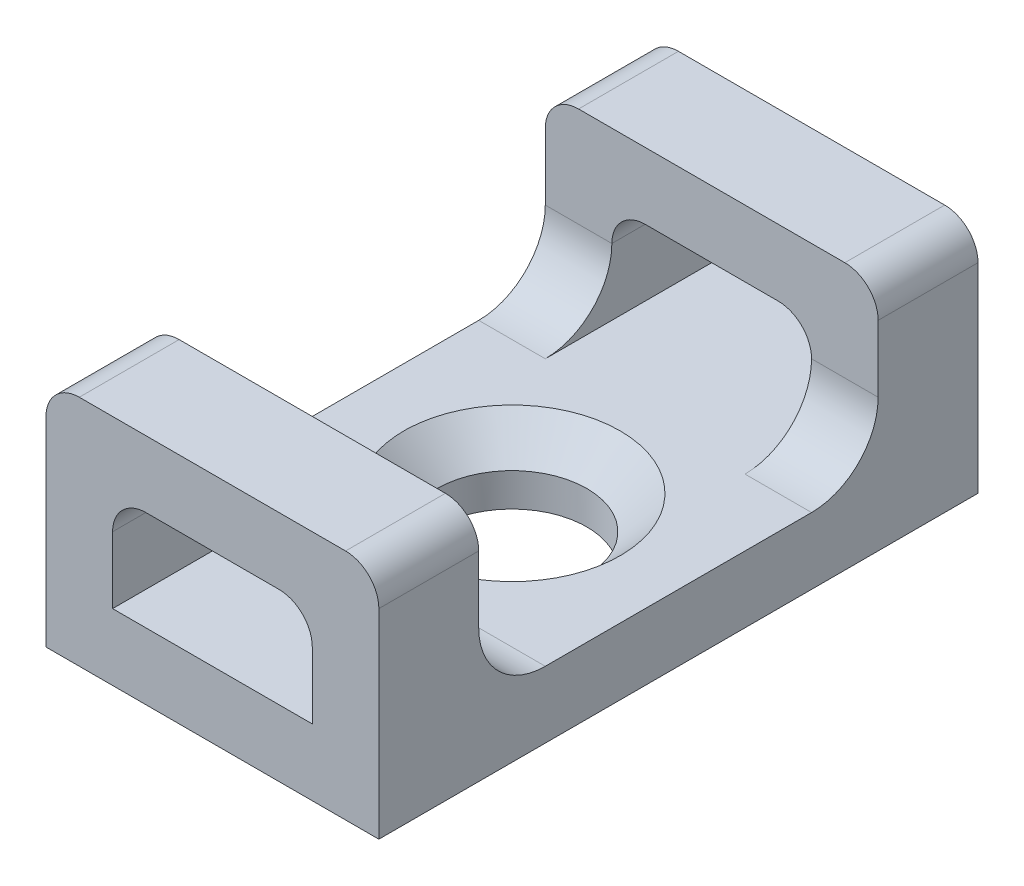
SolidWorks part; units mm, degrees
note: The reader was unsure of these and kept them because the rebuilt part matched: shared geometry of "Эскиз4<3>".
ref_plane "Спереди" through (0, 0, 0) normal (0, 0, 1) x (1, 0, 0)
ref_plane "Сверху" through (0, 0, 0) normal (0, 1, 0) x (1, 0, 0)
ref_plane "Справа" through (0, 0, 0) normal (1, 0, 0) x (0, 0, -1)
sketch "Эскиз1" plane through (0, 0, 0) normal (0, 1, 0) x (1, 0, 0)
  line L1 (0, 0) -> (10, 0)
  line L2 (0, 0) -> (0, 18)
  line L3 (0, 18) -> (10, 18)
  line L4 (10, 0) -> (10, 18)
  dimension "D1" = 18
  dimension "D2" = 10
extrude "Бобышка-Вытянуть1" add sketch "Эскиз1" along normal blind 2
sketch "Эскиз2" plane through (0, 2, 0) normal (0, 1, 0) x (1, 0, 0)
  line L0 (0, 0) -> (10, 0) construction
  line L1 (0, 18) -> (0, 0) construction
  circle A0 centre (5, 9) radius 2.25
  point P5 (5, 0)
  point P9 (0, 9)
  dimension "D1" = 4.5
extrude "Вырез-Вытянуть1" cut sketch "Эскиз2" against normal blind 2
sketch "Эскиз4" plane through (0, 0, 0) normal (0, 0, 1) x (1, 0, 0)
  line L0 (0, 2) -> (10, 2) construction
  line L1 (0, 2) -> (2, 2)
  line L2 (0, 2) -> (0, 6)
  line L3 (1, 7) -> (2, 7)
  line L4 (2, 2) -> (2, 4)
  line L5 (10, 2) -> (8, 2)
  line L6 (10, 2) -> (10, 6)
  line L7 (9, 7) -> (8, 7)
  line L8 (8, 2) -> (8, 4)
  line L9 (2, 7) -> (8, 7)
  line L10 (2, 7) -> (2, 5)
  line L11 (3, 5) -> (7, 5)
  line L12 (8, 7) -> (8, 5)
  arc A0 (10, 6) -> (9, 7) centre (9, 6) ccw
  arc A1 (1, 7) -> (0, 6) centre (1, 6) ccw
  arc A2 (8, 4) -> (7, 5) centre (7, 4) ccw
  arc A3 (2, 4) -> (3, 5) centre (3, 4) cw
  point P17 (10, 7)
  point P20 (0, 7)
  dimension "D4" = 1
  dimension "D1" = 3
  dimension "D3" = 2
extrude "Бобышка-Вытянуть2" add sketch "Эскиз4" against normal blind 3
chamfer "Фаска1" distance 1 angle 45 1 edges at (5, 2, -6.75)
extrude "Бобышка-Вытянуть3" add sketch "Эскиз4<3>" along normal blind 3 from vertex
sketch "Эскиз4<3>" plane through (0, 0, 0) normal (0, 0, 1) x (1, 0, 0) same geometry as "Эскиз4"
fillet "Скругление1" radius 2 4 edges at (9, 2, -3) (1, 2, -3) (1, 2, -15) (9, 2, -15)
